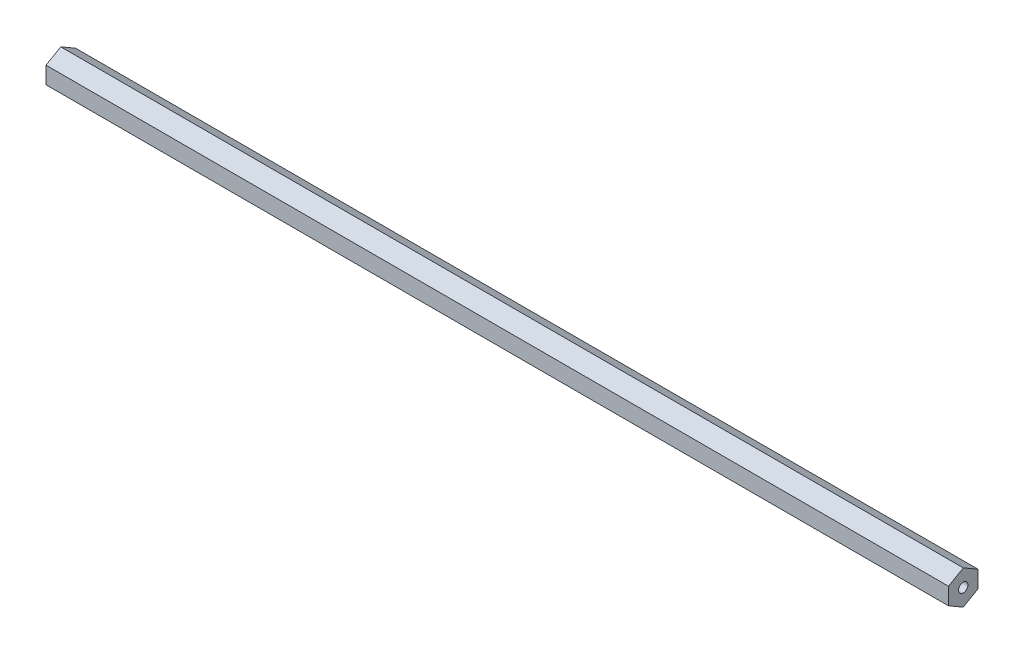
SolidWorks part; units mm, degrees
material "7075-T6 (SN)"
ref_plane "Front Plane" through (0, 0, 0) normal (0, 0, 1) x (1, 0, 0)
ref_plane "Top Plane" through (0, 0, 0) normal (0, 1, 0) x (1, 0, 0)
ref_plane "Right Plane" through (0, 0, 0) normal (1, 0, 0) x (0, 0, -1)
sketch "Sketch1" plane through (0, 0, 0) normal (1, 0, 0) x (0, 0, -1)
  line L1 (0, 7.3323) -> (-6.35, 3.6662)
  line L2 (-6.35, 3.6662) -> (-6.35, -3.6662)
  line L3 (-6.35, -3.6662) -> (0, -7.3323)
  line L4 (0, -7.3323) -> (6.35, -3.6662)
  line L5 (6.35, -3.6662) -> (6.35, 3.6662)
  line L6 (6.35, 3.6662) -> (0, 7.3323)
  circle A2 centre (0, 0) radius 6.35 construction
  dimension "D2" = 12.7
extrude "Boss-Extrude1" add sketch "Sketch1" along normal mid plane 388.874 contours L5 L6 L1 L2 L3 L4 region at (0, 0, 0)
hole_wizard "#10-32 Tapped Hole2" positions "3DSketch2" profile "Sketch5" tap size "#10-32" standard "ANSI Inch"
sketch3d "3DSketch2"
  point P0 (194.437, 0, 0)
  point P12 (-194.437, 0, 0)
sketch "Sketch5" plane through (194.437, 0, 0) normal (0, 1, 0) x (0, 0, -1)
  line L0 (0, 0) -> (0, 17.5608)
  line L1 (0, 17.5608) -> (2.0193, 16.3474)
  line L2 (2.0193, 16.3474) -> (2.0193, 0)
  line L5 (2.0193, 0) -> (0, 0)
  line L10 (0, 17.5608) -> (-2.0193, 16.3474) construction
  line L11 (0, -6.35) -> (0, 107.95) construction
  dimension "Tap Drill Dia." = 4.0386
  dimension "Tap Drill Depth" = 16.3474
  dimension "Drill Angle" = 118
cosmetic thread "Hole Thread3" parameters "D1"=13.97, "D2"=4.826
cosmetic thread "Hole Thread4" parameters "D1"=13.97, "D2"=4.826
